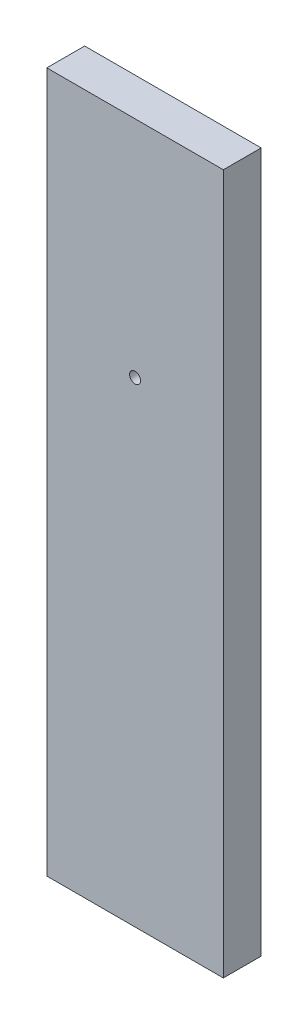
SolidWorks part; units mm, degrees
ref_plane "Front Plane" through (0, 0, 0) normal (0, 0, 1) x (1, 0, 0)
ref_plane "Top Plane" through (0, 0, 0) normal (0, 1, 0) x (1, 0, 0)
ref_plane "Right Plane" through (0, 0, 0) normal (1, 0, 0) x (0, 0, -1)
sketch "Sketch1" plane through (0, 0, 0) normal (0, 1, 0) x (1, 0, 0)
  line L1 (0, 0) -> (88.9, 0)
  line L2 (0, 0) -> (0, 19.05)
  line L3 (0, 19.05) -> (88.9, 19.05)
  line L4 (88.9, 0) -> (88.9, 19.05)
  dimension "D1" = 19.05
  dimension "D2" = 88.9
extrude "Boss-Extrude1" add sketch "Sketch1" along normal blind 352.522
sketch "Sketch2" plane through (0, 0, 0) normal (0, 0, 1) x (1, 0, 0)
  line L0 (44.45, 352.522) -> (44.45, 239.6416) construction
  line L1 (0, 352.522) -> (88.9, 352.522) construction
  line L2 (44.45, 0) -> (44.45, 239.6416) construction
  line L3 (0, 0) -> (88.9, 0) construction
  circle A0 centre (44.45, 239.6416) radius 2.7781
  point P6 (0, 0)
  dimension "D1" = 5.5562
  dimension "D3" = 239.6416
extrude "Cut-Extrude1" cut sketch "Sketch2" against normal through all contours A0 L0 L2 region at (44.45, 239.6416, 0)
